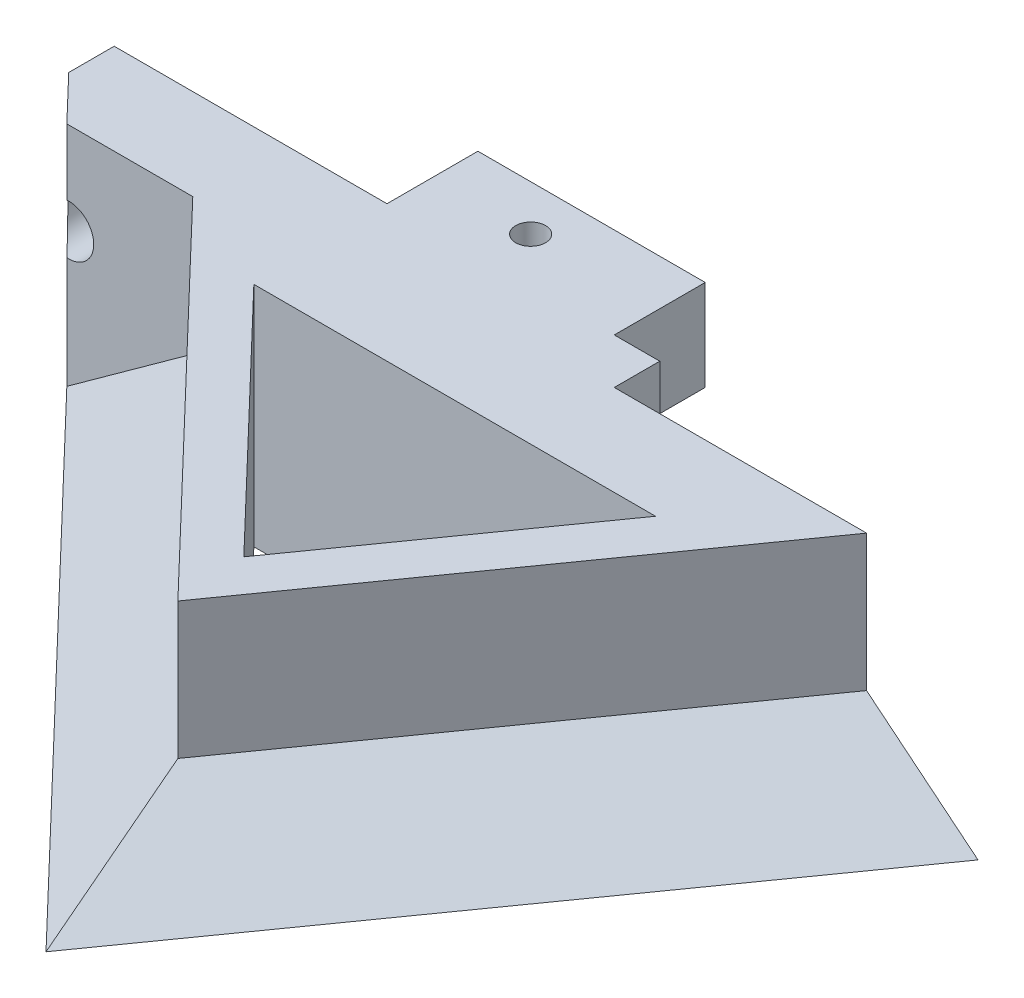
SolidWorks part; units mm, degrees
ref_plane "Front Plane" through (0, 0, 0) normal (0, 0, 1) x (1, 0, 0)
ref_plane "Top Plane" through (0, 0, 0) normal (0, 1, 0) x (1, 0, 0)
ref_plane "Right Plane" through (0, 0, 0) normal (1, 0, 0) x (0, 0, -1)
sketch "Sketch2" plane through (0, 0, 0) normal (0, 1, 0) x (1, 0, 0)
  line L0 (0, 0) -> (0, -76.2) construction
  line L1 (-69.85, 0) -> (0, 0) construction
  line L2 (-69.85, 6.35) -> (-76.2, 6.35)
  line L3 (-76.2, 6.35) -> (-76.2, 0)
  line L4 (-76.2, 0) -> (-69.85, 0) construction
  line L5 (-76.2, 0) -> (-127, 0)
  line L6 (-73.025, 0) -> (-73.025, -76.2) construction
  line L7 (-127, 0) -> (-73.025, -76.2)
  line L8 (-73.025, -76.2) -> (0, 0)
  line L9 (-38.5563, -12.7) -> (-69.85, -12.7)
  line L10 (-76.2, -12.7) -> (-69.85, -12.7)
  line L11 (-76.2, -12.7) -> (-94.6593, -12.7)
  line L12 (-69.85, 0) -> (-69.85, 6.35) construction
  line L13 (-69.85, 6.35) -> (-69.85, 19.05)
  line L14 (-69.85, 19.05) -> (-38.1, 19.05)
  line L15 (-38.1, 19.05) -> (-38.1, 6.35)
  line L16 (-38.1, 6.35) -> (-38.1, 0) construction
  line L17 (-69.85, 6.35) -> (-38.1, 6.35) construction
  line L18 (-69.85, 12.7) -> (-51.816, 12.7) construction
  line L20 (-70.8155, -46.3618) -> (-38.5563, -12.7)
  line L21 (0, 0) -> (0, 6.35)
  line L22 (-38.1, 6.35) -> (0, 6.35)
  line L23 (0, 6.35) -> (6.0854, 6.35) construction
  line L24 (-94.6593, -12.7) -> (-70.8155, -46.3618)
  line L25 (0, 0) -> (6.0854, 6.35) construction
  line L26 (-111.4547, 11.0112) -> (-70.8155, -46.3618) construction
  line L27 (-70.8155, -46.3618) -> (-13.7539, 13.1808) construction
  circle A0 centre (-51.816, 12.7) radius 2.0828
  dimension "D2" = 69.85
  dimension "D3" = 6.35
  dimension "D4" = 50.8
extrude "Boss-Extrude1" add sketch "Sketch2" along normal blind 31.75
sketch "Sketch3" plane through (0, 31.75, 0) normal (0, 1, 0) x (1, 0, 0)
  line L0 (-127, 0) -> (-73.025, -76.2)
  line L1 (-73.025, -76.2) -> (-6.0854, -6.35)
  line L2 (-23.6757, -6.35) -> (-6.0854, -6.35)
  line L3 (-38.5563, -12.7) -> (-26.3855, 0) construction
  line L5 (-111.4367, 0) -> (-127, 0)
  line L6 (-94.6593, -12.7) -> (-103.6551, 0) construction
  line L7 (-71.552, -56.3079) -> (-111.4367, 0)
  line L8 (-76.2, 0) -> (-127, 0) construction
  line L11 (-71.552, -56.3079) -> (-23.6757, -6.35)
sketch "Sketch4" plane through (0, 0, 0) normal (0, -1, 0) x (1, 0, 0)
  line L0 (-38.1, -6.35) -> (-69.85, -6.35)
  line L1 (-69.85, -6.35) -> (-69.85, -19.05)
  line L2 (-69.85, -19.05) -> (-38.1, -19.05)
  line L3 (-38.1, -19.05) -> (-38.1, -6.35)
extrude "Cut-Extrude1" cut sketch "Sketch4" against normal blind 19.05
sketch "Sketch5" plane through (0, 19.05, 0) normal (0, -1, 0) x (-1, 0, 0)
  circle A0 centre (51.816, 12.7) radius 2.0828 construction
  circle A1 centre (51.816, 12.7) radius 3.4925
extrude "Cut-Extrude2" cut sketch "Sketch5" against normal blind 6.35
sketch "Sketch6" plane through (0, 0, -6.35) normal (0, 0, -1) x (-1, 0, 0)
  line L1 (0, 31.75) -> (0, 0) construction
  line L3 (6.35, 31.75) -> (6.35, 19.05) construction
  line L4 (0, 31.75) -> (38.1, 31.75) construction
  line L5 (0, 19.05) -> (6.35, 19.05) construction
  circle A0 centre (6.35, 19.05) radius 3.4925
extrude "Cut-Extrude6" cut sketch "Sketch3" against normal blind 19.05
chamfer "Chamfer5" distance 12.7 angle 45 1 edges at (-39.5552, 12.7, 41.275)
chamfer "Chamfer7" distance 12.7 angle 45 1 edges at (-103.7504, 12.7, 32.8229)
extrude "Cut-Extrude8" cut sketch "Sketch6" against normal blind 25.4
sketch "Sketch15" plane through (0, 0, -6.35) normal (0, 0, -1) x (-1, 0, 0)
  circle A0 centre (6.35, 19.05) radius 3.4925
  circle A1 centre (6.35, 19.05) radius 2.0828
extrude "Boss-Extrude2" add sketch "Sketch15" against normal blind 6.35
sketch "Sketch14" plane through (0, 0, -6.35) normal (0, 0, -1) x (-1, 0, 0)
  line L0 (0, 0) -> (11.43, 0)
  line L1 (0, 0) -> (76.2, 0) construction
  line L2 (11.43, 0) -> (11.43, 13.97)
  line L3 (11.43, 13.97) -> (0, 13.97)
  line L4 (0, 31.75) -> (0, 0) construction
  line L5 (0, 13.97) -> (0, 0)
extrude "Cut-Extrude10" cut sketch "Sketch14" against normal blind 6.35
mirror "Mirror1" about plane through (0, 31.75, 0) normal (-1, 0, 0) of bodies 113
delete or keep bodies "Body-Delete/Keep 1" type delete bodies bodies 113
